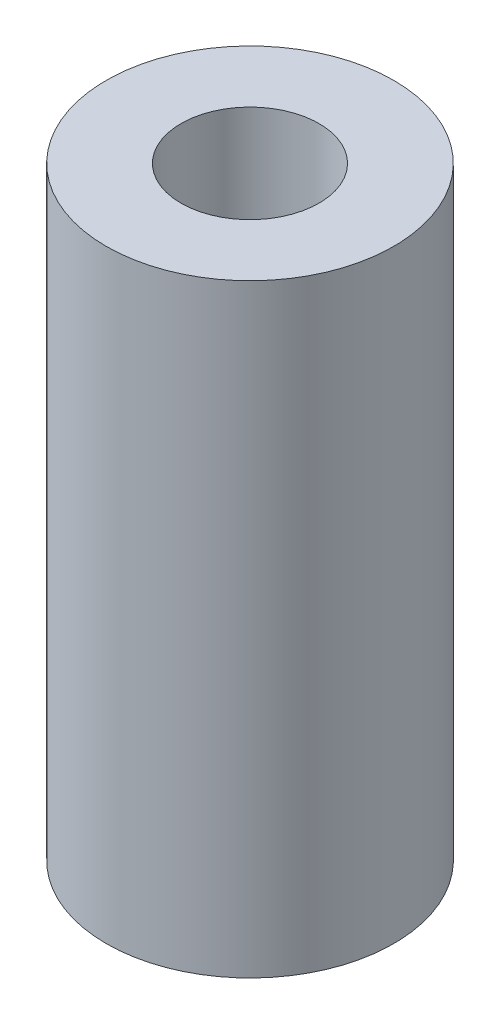
SolidWorks part; units mm, degrees
ref_plane "Front Plane" through (0, 0, 0) normal (0, 0, 1) x (1, 0, 0)
ref_plane "Top Plane" through (0, 0, 0) normal (0, 1, 0) x (1, 0, 0)
ref_plane "Right Plane" through (0, 0, 0) normal (1, 0, 0) x (0, 0, -1)
sketch "Sketch1" plane through (0, 0, 0) normal (0, 1, 0) x (1, 0, 0)
  circle A0 centre (0, 0) radius 2.5
  dimension "D1" = 5
extrude "Boss-Extrude1" add sketch "Sketch1" along normal mid plane 10.5
hole_wizard "M2 Clearance Hole1" positions "Sketch2" profile "Sketch3" hole size "M2" standard "ANSI Metric" end condition through all
sketch "Sketch2" plane through (0, 5.25, 0) normal (0, 1, 0) x (1, 0, 0)
  point P0 (0, 0)
sketch "Sketch3" plane through (0, 5.25, 0) normal (1, 0, 0) x (0, 0, 1)
  line L0 (0, 0) -> (0, 10.5)
  line L1 (0, 10.5) -> (1.2, 10.5)
  line L2 (1.2, 10.5) -> (1.2, 0)
  line L5 (1.2, 0) -> (0, 0)
  line L11 (0, -6.35) -> (0, 107.95) construction
  dimension "Thru Hole Dia." = 2.4
  dimension "Thru Hole Depth" = 10.5
